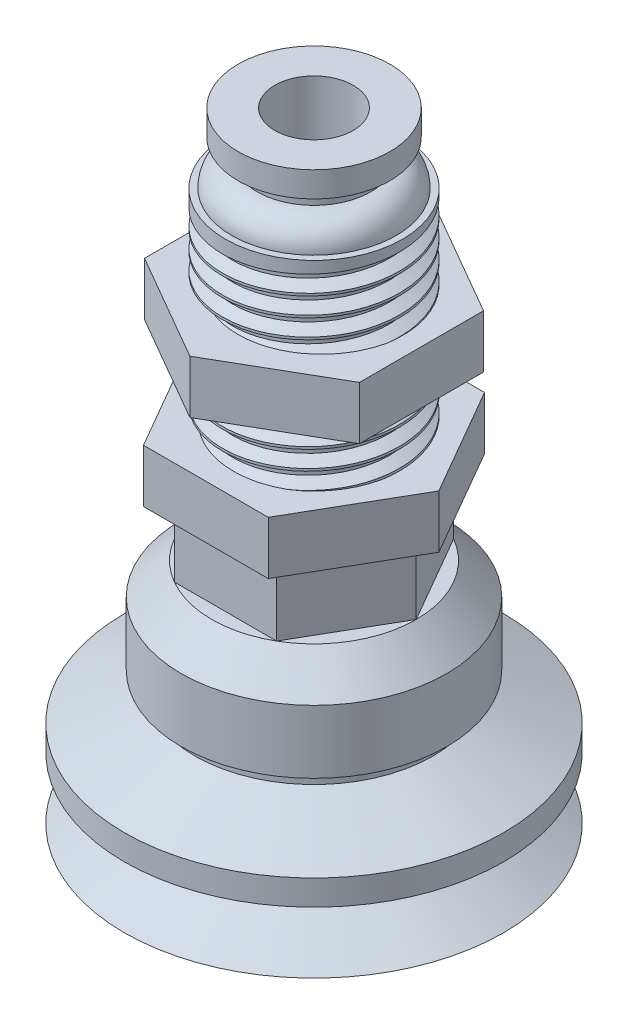
SolidWorks part; units mm, degrees
ref_plane "Front Plane" through (0, 0, 0) normal (0, 0, 1) x (1, 0, 0)
ref_plane "Top Plane" through (0, 0, 0) normal (0, 1, 0) x (1, 0, 0)
ref_plane "Right Plane" through (0, 0, 0) normal (1, 0, 0) x (0, 0, -1)
sketch "Sketch1" plane through (0, 0, 0) normal (0, 1, 0) x (1, 0, 0)
  circle A0 centre (0, 0) radius 7
  dimension "D1" = 14
extrude "Boss-Extrude1" add sketch "Sketch1" along normal blind 20
thread "Thread1" pitch 1.5 method cut profile "Thread Profile1" start angle 0, offset 0, length 20, pitch 1.5, diameter 14
ref_plane "Plane1" through (-7, 20, 0) normal (0, 0, 1) x (-1, 0, 0)
sketch "Thread Profile1" plane through (-7, 20, 0) normal (0, 0, 1) x (-1, 0, 0)
  line L0 (0, 0) -> (0, 1.5) construction
  line L11 (0, 0) -> (0, 1.3125)
  line L12 (0, 1.3125) -> (-0.8119, 0.8437)
  line L13 (-0.8119, 0.8437) -> (-0.8119, 0.4687)
  line L15 (-0.8119, 0.4687) -> (0, 0)
  line L17 (-0.8119, 0.6562) -> (0, 0.6562) construction
  point P2 (0, 0)
  dimension "Pitch" = 1.5
  dimension "Profile_Angle" = 60
  dimension "Profile_Land" = 0.375
  dimension "Profile_Height" = 0.8119
sketch "Sketch2" plane through (0, 0, 0) normal (0, -1, 0) x (1, 0, 0)
  line L1 (8.0829, 0) -> (4.0415, 7)
  line L2 (4.0415, 7) -> (-4.0415, 7)
  line L3 (-4.0415, 7) -> (-8.0829, 0)
  line L4 (-8.0829, 0) -> (-4.0415, -7)
  line L5 (-4.0415, -7) -> (4.0415, -7)
  line L6 (4.0415, -7) -> (8.0829, 0)
  circle A0 centre (0, 0) radius 7 construction
  dimension "D1" = 14
extrude "Boss-Extrude2" add sketch "Sketch2" along normal blind 5.5
sketch "Sketch3" plane through (0, 0, 0) normal (0, 0, 1) x (1, 0, 0)
  line L0 (4.2, 23) -> (4.5, 23)
  line L1 (4.5, 23) -> (4.5, 22)
  line L2 (7, 20) -> (-7, 20) construction
  line L3 (6.5, 20) -> (0, 20)
  line L4 (0, 23) -> (0, 20)
  line L5 (0, 23) -> (0, 25.5)
  line L6 (4.2, 23) -> (4.2, 23.5)
  line L7 (4.2, 23.5) -> (6, 23.5)
  line L8 (6, 23.5) -> (6, 25.5)
  line L9 (6, 25.5) -> (0, 25.5)
  line L10 (0, 23) -> (4.2, 23) construction
  line L11 (8.0829, -5.5) -> (10.5, -8)
  line L12 (10.5, -8) -> (10.5, -13)
  line L13 (10.5, -13) -> (9.4046, -13.7)
  line L14 (9.4046, -13.7) -> (9.4046, -14.2)
  line L15 (9.4046, -14.2) -> (15, -16.644)
  line L16 (15, -16.644) -> (15, -18.644)
  line L17 (15, -18.644) -> (11, -21.2)
  line L18 (11, -21.2) -> (15, -23.5)
  line L19 (15, -23.5) -> (0, -23.5)
  line L20 (0, -23.5) -> (0, -5.5)
  line L21 (4.0415, -5.5) -> (-4.0415, -5.5) construction
  line L22 (0, -5.5) -> (8.0829, -5.5)
  arc A0 (4.5, 22) -> (6.5, 20) centre (4.5, 20) cw
  point P9 (0, 0)
  point P11 (0, 20)
  point P31 (0, 0)
  point P34 (22.1497, -19.8825)
  dimension "D1" = 6
  dimension "D2" = 1
  dimension "D3" = 3
  dimension "D4" = 2
  dimension "D5" = 2.5
  dimension "D6" = 4.2
  dimension "D7" = 6.5
  dimension "D8" = 18
  dimension "D9" = 8.7
  dimension "D10" = 10.5
  dimension "D11" = 15
  dimension "D12" = 11
  dimension "D13" = 7
  dimension "D14" = 5
  dimension "D15" = 2.5
  dimension "D16" = 0.5
  dimension "D17" = 2
  dimension "D18" = 1.3
revolve "Revolve1" add sketch "Sketch3" angle 360 about L4
sketch "Sketch6" plane through (0, 0, 0) normal (0, 1, 0) x (1, 0, 0)
  line L1 (9.8727, 0) -> (4.9363, 8.55)
  line L2 (4.9363, 8.55) -> (-4.9363, 8.55)
  line L3 (-4.9363, 8.55) -> (-9.8727, 0)
  line L4 (-9.8727, 0) -> (-4.9363, -8.55)
  line L5 (-4.9363, -8.55) -> (4.9363, -8.55)
  line L6 (4.9363, -8.55) -> (9.8727, 0)
  circle A0 centre (0, 0) radius 8.55 construction
  dimension "D1" = 17.1
extrude "Boss-Extrude3" add sketch "Sketch6" along normal blind 4.2
ref_plane "Plane2" through (0, 9.2, 0) normal (0, 1, 0) x (1, 0, 0)
sketch "Sketch7" plane through (0, 9.2, 0) normal (0, 1, 0) x (1, 0, 0)
  line L1 (0, 9.815) -> (-8.5, 4.9075)
  line L2 (-8.5, 4.9075) -> (-8.5, -4.9075)
  line L3 (-8.5, -4.9075) -> (0, -9.815)
  line L4 (0, -9.815) -> (8.5, -4.9075)
  line L5 (8.5, -4.9075) -> (8.5, 4.9075)
  line L6 (8.5, 4.9075) -> (0, 9.815)
  circle A0 centre (0, 0) radius 8.5 construction
  dimension "D1" = 17
extrude "Boss-Extrude4" add sketch "Sketch7" along normal blind 4.2
sketch "Sketch5" plane through (0, 25.5, 0) normal (0, 1, 0) x (1, 0, 0)
  circle A0 centre (0, 0) radius 3.1
  dimension "D1" = 6.2
extrude "Cut-Extrude1" cut sketch "Sketch5" against normal through all
